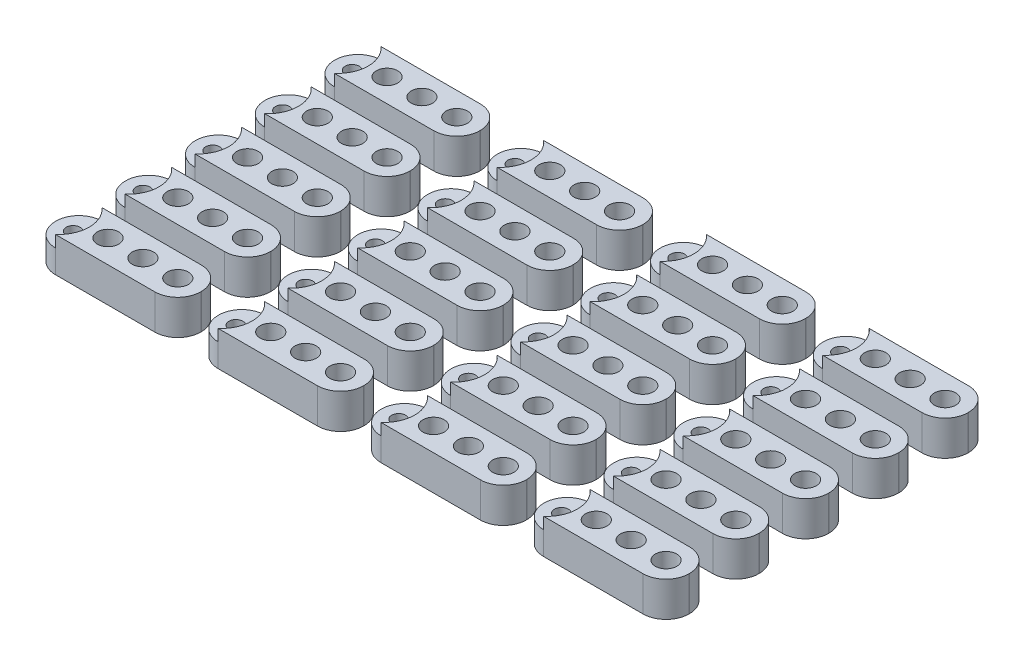
SolidWorks part; units mm, degrees
ref_plane "Front Plane" through (0, 0, 0) normal (0, 0, 1) x (1, 0, 0)
ref_plane "Top Plane" through (0, 0, 0) normal (0, 1, 0) x (1, 0, 0)
ref_plane "Right Plane" through (0, 0, 0) normal (1, 0, 0) x (0, 0, -1)
sketch "Sketch1" plane through (0, 0, 0) normal (0, 1, 0) x (1, 0, 0)
  line L1 (-2.76, 1) -> (1.51, 1)
  line L2 (-3.75, 0.01) -> (-3.75, -0.01)
  line L3 (-2.76, -1) -> (1.51, -1)
  line L4 (2.5, 0.01) -> (2.5, -0.01)
  circle A0 centre (0, 0) radius 0.46
  circle A1 centre (1.5, 0) radius 0.46
  circle A2 centre (-1.5, 0) radius 0.46
  circle A3 centre (-3, 0) radius 0.3
  arc A4 (1.51, -1) -> (2.5, -0.01) centre (1.51, -0.01) ccw
  arc A5 (2.5, 0.01) -> (1.51, 1) centre (1.51, 0.01) ccw
  arc A6 (-2.76, -1) -> (-3.75, -0.01) centre (-2.76, -0.01) cw
  arc A7 (-3.75, 0.01) -> (-2.76, 1) centre (-2.76, 0.01) cw
  arc A8 (-2.76, 1) -> (-2.76, -1) centre (-3.6399, 0) cw
  point P19 (-3.75, -1)
  point P22 (-3.75, 1)
  dimension "D1" = 0.99
  dimension "D3" = 1
  dimension "D4" = 2
  dimension "D5" = 0.75
  dimension "D6" = 1
extrude "Boss-Extrude1" add sketch "Sketch1" along normal blind 1.5 contours L1 A8 L3 A4 L4 A5 A0 A1 A2 region at (-0.625, 0, -0.9437)
extrude "Boss-Extrude2" add sketch "Sketch1<3>" along normal blind 1 contours A8 A7 L2 A6 A3 region at (-2.3326, 0, 0)
sketch "Sketch1<3>" plane through (0, 0, 0) normal (0, 1, 0) x (1, 0, 0) same geometry as "Sketch1"
sketch "Sketch2" plane through (0, 0, 0) normal (0, 1, 0) x (1, 0, 0)
  line L0 (0, 0) -> (-4.3842, 0) construction
  line L1 (0, 0) -> (0, -2.5212) construction
pattern_linear "LPattern1" count 5 spacing 3 along (0, 0, 1) count 4 spacing 7 along (1, 0, 0) of bodies 102
